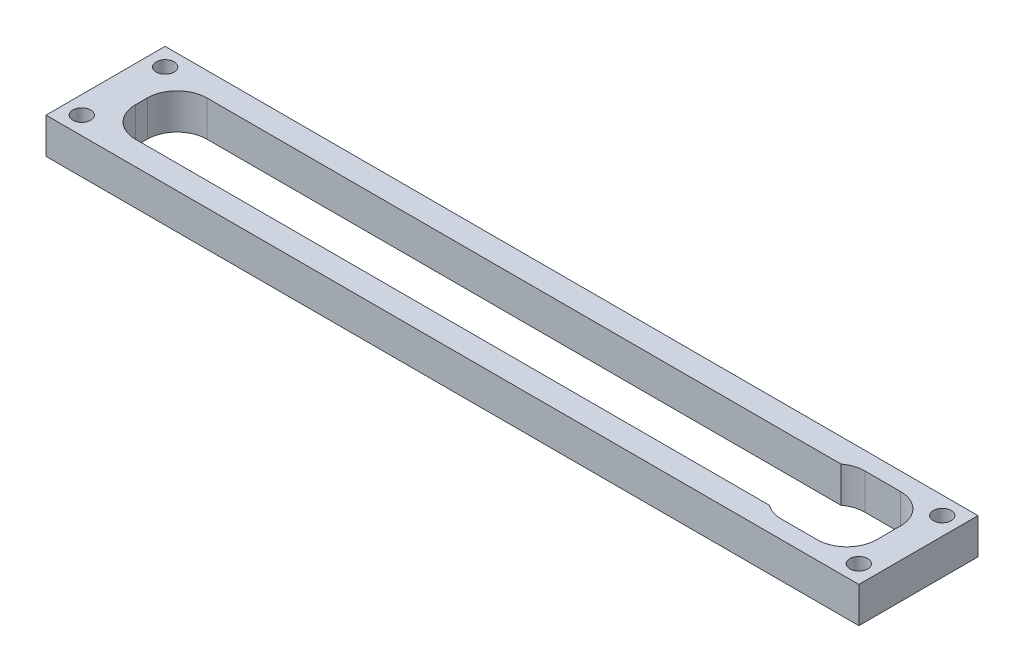
SolidWorks part; units mm, degrees
ref_plane "Front Plane" through (0, 0, 0) normal (0, 0, 1) x (1, 0, 0)
ref_plane "Top Plane" through (0, 0, 0) normal (0, 1, 0) x (1, 0, 0)
ref_plane "Right Plane" through (0, 0, 0) normal (1, 0, 0) x (0, 0, -1)
sketch "Sketch1" plane through (0, 0, 0) normal (0, 1, 0) x (1, 0, 0)
  line L0 (68.2139, 20) -> (68.2139, 0) construction
  line L1 (0, 0) -> (136.4278, 0)
  line L2 (0, 0) -> (0, 20)
  line L3 (0, 20) -> (136.4278, 20)
  line L4 (136.4278, 0) -> (136.4278, 20)
  line L5 (0, 10) -> (136.4278, 10) construction
  line L6 (68.2139, 16) -> (68.2139, 4) construction
  line L7 (6, 16) -> (130.4278, 16)
  line L8 (6, 16) -> (6, 4)
  line L9 (6, 4) -> (130.4278, 4)
  line L10 (130.4278, 16) -> (130.4278, 4)
  line L11 (6, 10) -> (130.4278, 10) construction
  circle A0 centre (3, 17) radius 1.5
  circle A1 centre (3, 3) radius 1.5
  circle A2 centre (133.4278, 3) radius 1.5
  circle A3 centre (133.4278, 17) radius 1.5
  point P17 (68.2139, 10)
  point P18 (68.2139, 10)
  dimension "D7" = 3
  dimension "D1" = 136.4278
  dimension "D2" = 20
  dimension "D3" = 124.4278
  dimension "D4" = 12
  dimension "D5" = 3
  dimension "D6" = 3
extrude "Boss-Extrude1" add sketch "Sketch1" along normal blind 6
sketch "Sketch2" plane through (0, 6, 0) normal (0, 1, 0) x (1, 0, 0)
  line L0 (92, 10) -> (-49908, 10) construction
  line L1 (130.4278, 4) -> (130.4278, 16) construction
  line L2 (117.4278, 17) -> (117.4278, 16)
  line L5 (130.4278, 16) -> (6, 16) construction
  line L6 (124.4278, 17) -> (124.4278, 3) construction
  line L7 (117.4278, 17) -> (131.4278, 17)
  line L9 (117.4278, 3) -> (131.4278, 3)
  line L10 (131.4278, 17) -> (131.4278, 3)
  line L12 (117.4278, 16) -> (130.4278, 16)
  line L13 (130.4278, 16) -> (130.4278, 4)
  line L14 (130.4278, 4) -> (117.4278, 4)
  line L15 (6, 4) -> (130.4278, 4) construction
  line L16 (117.4278, 4) -> (117.4278, 3)
  point P4 (130.4278, 10)
  point P23 (124.4278, 10)
  dimension "D1" = 1
  dimension "D2" = 14
  dimension "D3" = 14
extrude "Cut-Extrude1" cut sketch "Sketch2" against normal through all
fillet "Fillet1" radius 5 6 edges at (131.4278, 3, -17) (131.4278, 3, -3) (117.4278, 3, -17) (117.4278, 3, -3) (6, 3, -4) (6, 3, -16)
equation "\"TrackLength\"= ( ( \"n\" * 28 ) ) / cos ( \"MountAngle\" ) - ( 2 * \"x\" )"
equation "\"D1@Sketch1\"=\"TrackLength\""
equation "\"TrackWidth\"= \"MarbleTrackWidth\" + ( 2 * 4 )"
equation "\"D2@Sketch1\"=\"TrackWidth\""
equation "\"MarbleTrackWidth\"= \"MarbleWidth\" - 1"
equation "\"MarbleTrackLength\"= \"TrackLength\" - ( 2 * 6 )"
equation "\"D3@Sketch1\"=\"MarbleTrackLength\""
equation "\"D4@Sketch1\"=\"MarbleTrackWidth\""
equation "\"MarbleWidth\"= 13"
equation "\"n\"= 5"
equation "\"MountAngle\"= 5"
equation "\"x\"= 14 / cos ( \"MountAngle\" ) - 12"
